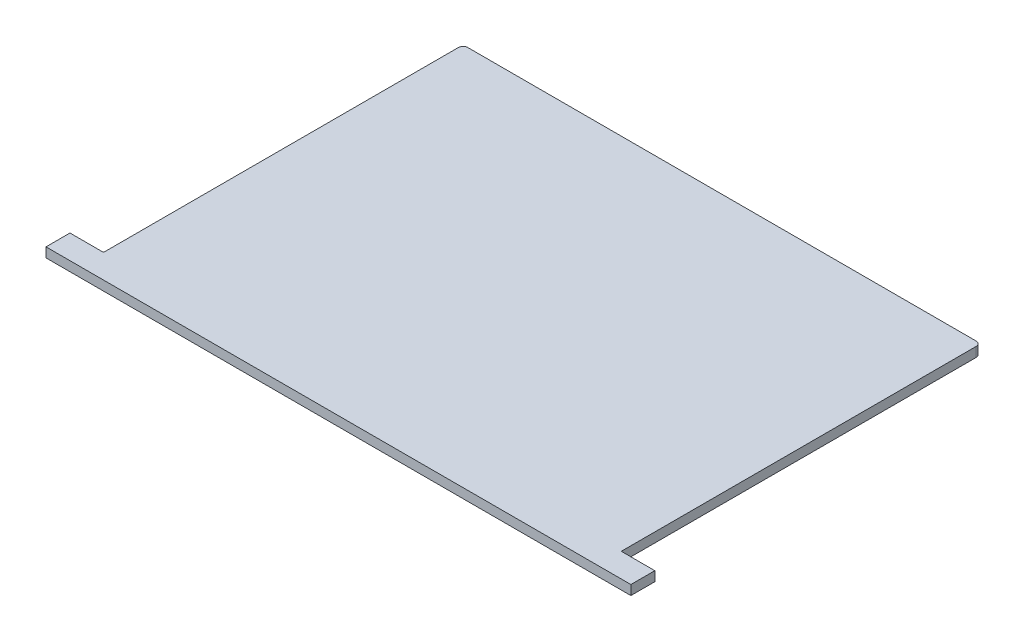
SolidWorks part; units mm, degrees
material "ABS"
ref_plane "Front Plane" through (0, 0, 0) normal (0, 0, 1) x (1, 0, 0)
ref_plane "Top Plane" through (0, 0, 0) normal (0, 1, 0) x (1, 0, 0)
ref_plane "Right Plane" through (0, 0, 0) normal (1, 0, 0) x (0, 0, -1)
sketch "Sketch1" plane through (0, 0, 0) normal (0, 1, 0) x (1, 0, 0)
  line L1 (-27, -20) -> (27, -20)
  line L3 (-27, 20) -> (27, 20)
  line L5 (-27, -20) -> (27, 20) construction
  line L6 (-27, 20) -> (27, -20) construction
  line L17 (-27, 20) -> (-27, -17.5)
  line L18 (-30.5, -17.5) -> (-30.5, -20)
  line L19 (-30.5, -20) -> (-27, -20)
  line L20 (-27, -17.5) -> (-30.5, -17.5)
  line L21 (27, 20) -> (27, -17.5)
  line L22 (27, -17.5) -> (30.5, -17.5)
  line L23 (30.5, -17.5) -> (30.5, -20)
  line L24 (30.5, -20) -> (27, -20)
  point P0 (0, 0)
  dimension "D1" = 2.5
  dimension "D2" = 3.5
  dimension "D3" = 54
  dimension "D4" = 40
  dimension "D5" = 3.5
  dimension "D6" = 2.5
extrude "Boss-Extrude1" add sketch "Sketch1" along normal blind 1
fillet "Fillet1" radius 0.5 2 edges at (27, 0.5, -20) (-27, 0.5, -20)
